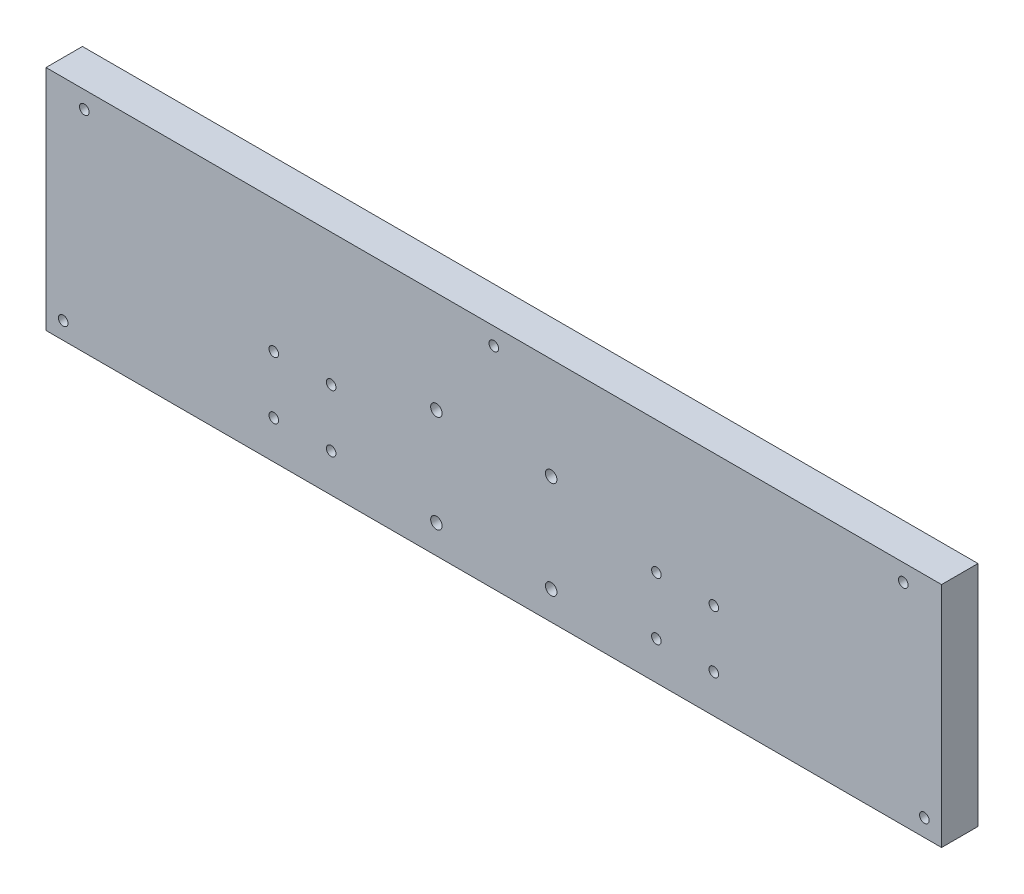
SolidWorks part; units mm, degrees
ref_plane "Front Plane" through (0, 0, 0) normal (0, 0, 1) x (1, 0, 0)
ref_plane "Top Plane" through (0, 0, 0) normal (0, 1, 0) x (1, 0, 0)
ref_plane "Right Plane" through (0, 0, 0) normal (1, 0, 0) x (0, 0, -1)
sketch "Sketch1" plane through (0, 0, 0) normal (0, 0, 1) x (1, 0, 0)
  line L1 (234.05, 0) -> (-234.05, 0)
  line L2 (234.05, 0) -> (234.05, 119.05)
  line L3 (234.05, 119.05) -> (-234.05, 119.05)
  line L4 (-234.05, 0) -> (-234.05, 119.05)
  line L5 (-234.05, 119.05) -> (234.05, 119.05) construction
  dimension "D1" = 119.05
  dimension "D2" = 468.1
extrude "Boss-Extrude1" add sketch "Sketch1" along normal blind 19.05
sketch "Sketch8" plane through (0, 0, 19.05) normal (0, 0, 1) x (1, 0, 0)
  circle A0 centre (-214.05, 110.05) radius 2.5
  circle A1 centre (0, 110.05) radius 2.5
  circle A2 centre (214.05, 110.05) radius 2.5
  circle A3 centre (-225.05, 9) radius 2.5
  circle A4 centre (225.05, 9) radius 2.5
hole_wizard "M5 Clearance Hole1" positions "Sketch2" profile "Sketch3" hole size "M5" standard "ANSI Metric"
sketch "Sketch2" plane through (0, 0, 0) normal (0, 0, -1) x (-1, 0, 0)
  point P0 (-115, 20)
  point P3 (-115, 50)
  point P6 (-85, 50)
  point P9 (-85, 20)
  point P12 (85, 20)
  point P15 (85, 50)
  point P18 (115, 50)
  point P21 (115, 20)
  point P25 (214.05, 110.05)
  point P28 (0, 110.05)
  point P31 (-214.05, 110.05)
  point P34 (-225.05, 9)
  point P37 (225.05, 9)
sketch "Sketch3" plane through (115, 20, 0) normal (1, 0, 0) x (0, 1, 0)
  line L0 (0, 0) -> (0, 30)
  line L1 (0, 30) -> (2.5, 28.4978)
  line L2 (2.5, 28.4978) -> (2.5, 0)
  line L5 (2.5, 0) -> (0, 0)
  line L10 (0, 30) -> (-2.5, 28.4978) construction
  line L11 (0, -6.35) -> (0, 107.95) construction
  dimension "Hole Dia." = 5
  dimension "Hole Depth" = 30
  dimension "Drill Angle" = 118
sketch "Sketch4" plane through (0, 0, 0) normal (0, 0, -1) x (-1, 0, 0)
  circle A0 centre (-30, 15) radius 3 construction
  circle A1 centre (-30, 66) radius 3 construction
  circle A2 centre (30, 66) radius 3 construction
  circle A3 centre (30, 15) radius 3 construction
  circle A4 centre (-30, 15) radius 3
  circle A5 centre (-30, 66) radius 3
  circle A6 centre (30, 66) radius 3
  circle A7 centre (30, 15) radius 3
hole_wizard "M5 Clearance Hole2" positions "Sketch5" profile "Sketch6" hole size "M5" standard "ANSI Metric"
sketch "Sketch5" plane through (0, 0, 0) normal (0, 0, -1) x (-1, 0, 0)
  point P0 (30, 15)
  point P3 (30, 66)
  point P6 (-30, 15)
  point P9 (-30, 66)
sketch "Sketch6" plane through (-30, 15, 0) normal (1, 0, 0) x (0, 1, 0)
  line L0 (0, 0) -> (0, 30)
  line L1 (0, 30) -> (3, 28.1974)
  line L2 (3, 28.1974) -> (3, 0)
  line L5 (3, 0) -> (0, 0)
  line L10 (0, 30) -> (-3, 28.1974) construction
  line L11 (0, -6.35) -> (0, 107.95) construction
  dimension "Hole Dia." = 6
  dimension "Hole Depth" = 30
  dimension "Drill Angle" = 118
